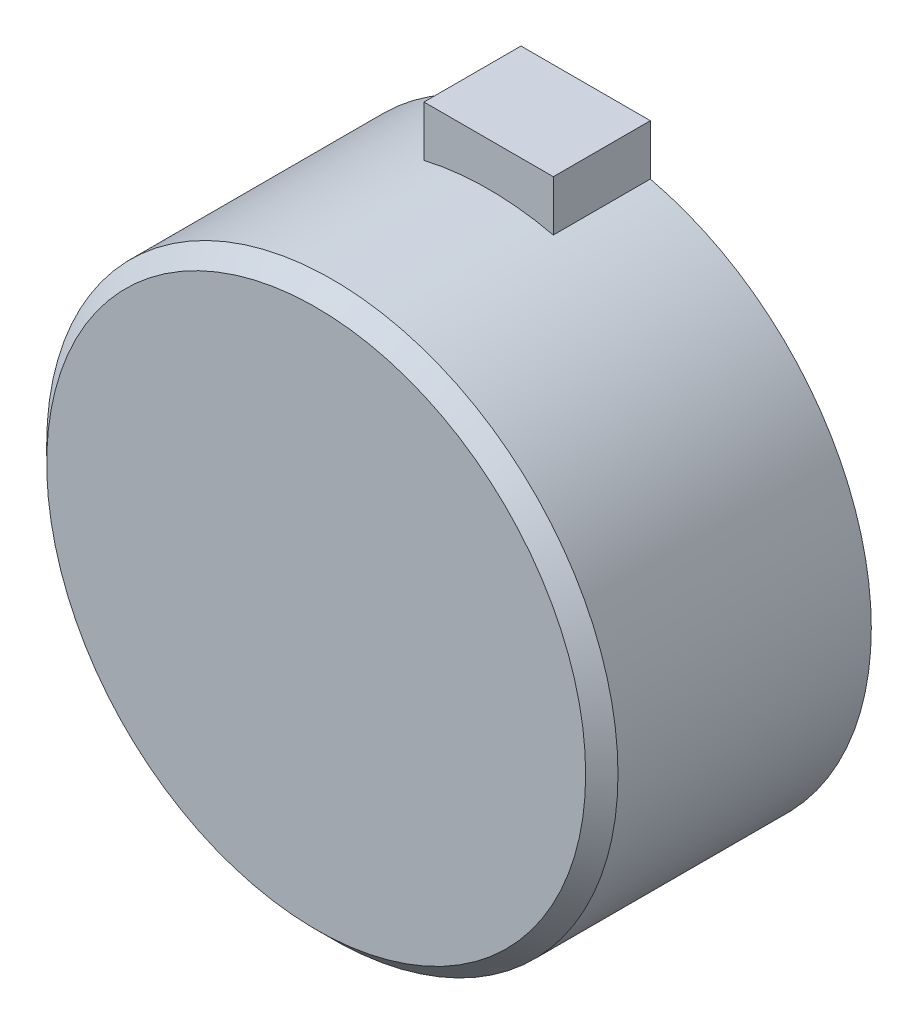
SolidWorks part; units mm, degrees
ref_plane "Front Plane" through (0, 0, 0) normal (0, 0, 1) x (1, 0, 0)
ref_plane "Top Plane" through (0, 0, 0) normal (0, 1, 0) x (1, 0, 0)
ref_plane "Right Plane" through (0, 0, 0) normal (1, 0, 0) x (0, 0, -1)
sketch "SK_Body" plane through (0, 0, 0) normal (0, 1, 0) x (1, 0, 0)
  line L0 (0, -10) -> (0, 60) construction
  line L1 (0, 0) -> (50, 0)
  line L2 (50, 0) -> (53, 3)
  line L3 (53, 3) -> (53, 50)
  line L4 (53, 50) -> (50, 50)
  line L5 (50, 50) -> (0, 50)
  line L6 (0, 50) -> (0, 0)
  dimension "P1" = 10
  dimension "P2" = 60
  dimension "R_front" = 50
  dimension "P4" = 53
  dimension "P5" = 3
  dimension "R_body" = 53
  dimension "L_body" = 50
  dimension "P8" = 50
  dimension "P9" = 50
  dimension "P10" = 50
revolve "Housing_Body" add sketch "SK_Body" angle 360 about L0
ref_plane "PL_Rear" through (0, 0, -50) normal (0, 0, 1) x (1, 0, 0)
sketch "SK_RearHole" plane through (0, 0, -50) normal (0, 0, 1) x (1, 0, 0)
  circle A0 centre (43, 0) radius 1.65
  dimension "D_rh" = 3.3
  dimension "R_rh" = 43
extrude "Rear_Tapped_Hole" cut sketch "SK_RearHole" along normal blind 8
ref_axis "AX_Joint" through (0, 0, -52.5) along (0, 0, 1)
pattern_circular "Rear_Hole_Pattern" count 8 over 360 about axis through (0, 0, -52.5) along (0, 0, 1) of "Rear_Tapped_Hole"
sketch "SK_Connector" plane through (0, 0, -50) normal (0, 0, 1) x (1, 0, 0)
  line L0 (-12, 49) -> (12, 49)
  line L1 (12, 49) -> (12, 61)
  line L2 (12, 61) -> (-12, 61)
  line L3 (-12, 61) -> (-12, 49)
  dimension "P1" = 12
  dimension "P2" = 49
  dimension "P3" = 12
  dimension "P4" = 49
  dimension "P5" = 12
  dimension "P6" = 61
  dimension "P7" = 12
  dimension "P8" = 61
extrude "Connector_Zone" add sketch "SK_Connector" along normal blind 18
equation "\"D_act\" = 106"
equation "\"L_housing\" = 50"
equation "\"PCD_rear\" = 86"
equation "\"D_rear_hole\" = 3.3"
equation "\"D_bearing_boss\" = 64"
equation "\"R_front@SK_Body\" = \"D_act\"/2-3.0"
equation "\"R_body@SK_Body\" = \"D_act\"/2"
equation "\"L_body@SK_Body\" = \"L_housing\""
equation "\"D_rh@SK_RearHole\" = \"D_rear_hole\""
equation "\"R_rh@SK_RearHole\" = \"PCD_rear\"/2"
